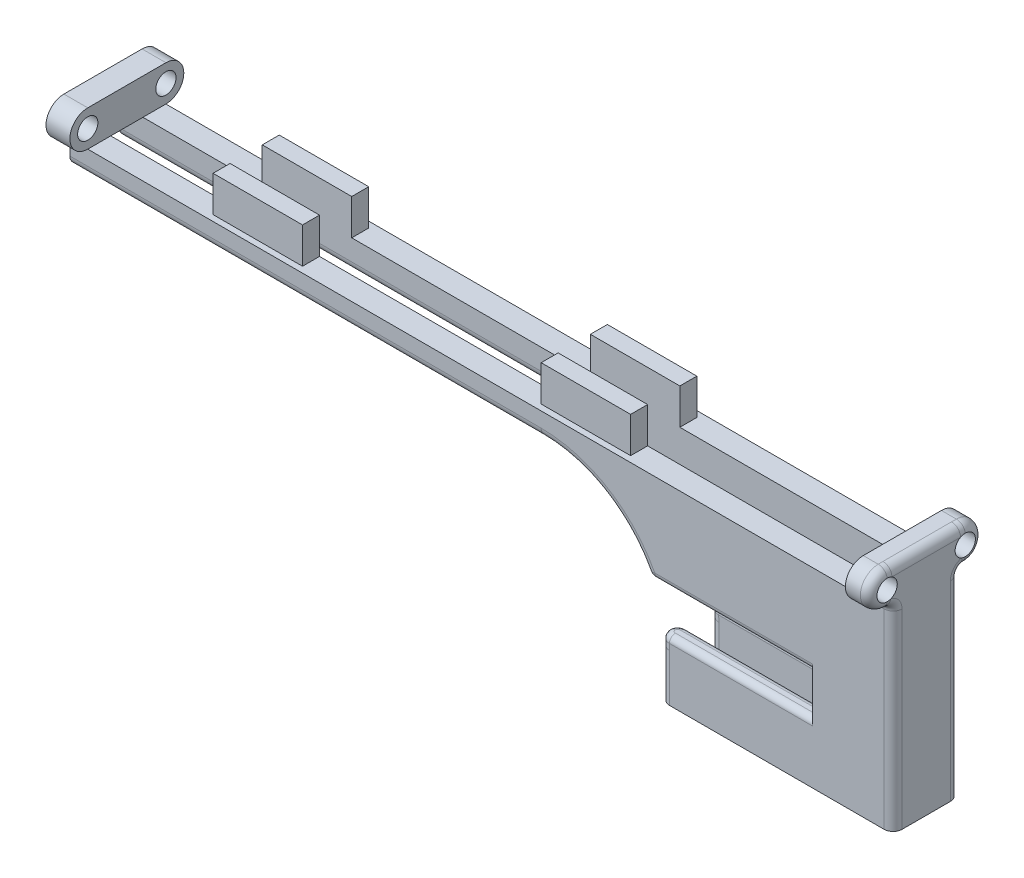
SolidWorks part; units mm, degrees
ref_plane "Plan de face" through (0, 0, 0) normal (0, 0, 1) x (1, 0, 0)
ref_plane "Plan de dessus" through (0, 0, 0) normal (0, 1, 0) x (1, 0, 0)
ref_plane "Plan de droite" through (0, 0, 0) normal (1, 0, 0) x (0, 0, -1)
sketch "Esquisse1" plane through (0, 0, 0) normal (0, 0, 1) x (1, 0, 0)
  line L0 (70, -6) -> (-40, -6) construction
  line L1 (25, -11) -> (-50, -11)
  line L3 (69.5003, -6) -> (40, -6)
  line L4 (-50, -11) -> (-50, -6)
  line L5 (69.5003, -6) -> (80, -6)
  line L6 (80, -6) -> (80, -31.0352)
  line L7 (70, -6) -> (-40, -6) construction
  line L8 (-50, 0) -> (-50, -6) construction
  line L9 (-30, -6) -> (-50, -6)
  line L11 (40, -6) -> (40, 0)
  line L12 (40, 0) -> (25, 0)
  line L13 (25, -6) -> (25, 0)
  line L15 (-15, -6) -> (-15, 0)
  line L16 (-15, 0) -> (-30, 0)
  line L17 (-30, -6) -> (-30, 0)
  line L18 (25, -6) -> (-15, -6)
  line L19 (40, 0) -> (40, -6) construction
  line L20 (40, 0) -> (40, -6) construction
  line L21 (-15, 0) -> (-15, -6) construction
  line L22 (45.0352, -31.0352) -> (80, -31.0352) construction
  line L23 (70.5, -22) -> (42.8822, -22)
  line L25 (70.5, -29) -> (70.5, -22)
  line L26 (70.5, -29) -> (44.9316, -29)
  line L28 (42.0815, -22.5) -> (16.9546, -22.5) construction
  line L32 (42.0815, -28.5) -> (16.9546, -28.5) construction
  line L33 (80, -31.0352) -> (80, -39)
  line L34 (80, -39) -> (45.0352, -39)
  line L35 (45.0352, -39) -> (45.0352, -31.0352)
  arc A4 (45.0352, -31.0352) -> (44.9316, -29) centre (25, -31.0352) ccw
  arc A5 (42.8822, -22) -> (25, -11) centre (25, -31.0352) ccw
  point P0 (24.6877, -7.875)
  dimension "D9" = 20.0352
  dimension "D1" = 5
  dimension "D6" = 75
  dimension "D7" = 0.5
  dimension "D8" = 0.5
  dimension "D10" = 9.5
  dimension "D11" = 10
extrude "Boss.-Extru.1" add sketch "Esquisse1" along normal blind 2.85
sketch "Esquisse2" plane through (80, 0, 0) normal (1, 0, 0) x (0, 0, -1)
  line L0 (0, -6) -> (1, -6)
  line L1 (0, -6) -> (0, -7)
  line L2 (0, -39) -> (0, -6) construction
  arc A0 (1, -6) -> (0, -7) centre (1, -7) ccw
  dimension "D1" = 1
extrude "Boss.-Extru.2" add sketch "Esquisse2" against normal up to surface (130 mm away) up to face at (-50, -8.5, 1.425)
ref_plane "Plan1" through (0, 0, 5.55) normal (0, 0, 1) x (1, 0, 0)
mirror "Symétrie4" about plane through (0, 0, 5.55) normal (0, 0, 1) of bodies 102
sketch "Esquisse3" plane through (80, 0, 0) normal (1, 0, 0) x (0, 0, -1)
  line L0 (0, -39) -> (0, -7) construction
  line L2 (-11.1, -39) -> (-11.1, -7) construction
  line L4 (0, -39) -> (0, -7)
  line L6 (-11.1, -39) -> (-11.1, -7)
  line L10 (-12.1, -6) -> (-12.1, 0) construction
  line L13 (78.6, 0) -> (-89.5, 0) construction
  line L14 (-5.55, 17.0694) -> (-5.55, -17.0694) construction
  line L15 (-12.1, 0) -> (1, 0)
  line L17 (0, -39) -> (-11.1, -39)
  arc A0 (1, -6) -> (0, -7) centre (1, -7) ccw construction
  arc A1 (-11.1, -7) -> (-12.1, -6) centre (-12.1, -7) ccw construction
  arc A2 (1, -6) -> (0, -7) centre (1, -7) ccw
  arc A3 (-11.1, -7) -> (-12.1, -6) centre (-12.1, -7) ccw
  arc A4 (-12.1, 0) -> (-12.1, -6) centre (-12.1, -3) ccw
  arc A5 (1, 0) -> (1, -6) centre (1, -3) cw
extrude "Boss.-Extru.3" add sketch "Esquisse3" along normal blind 4
hole_wizard "Dégagement M31" positions "Esquisse4" profile "Esquisse5" hole size "M3" standard "ISO" end condition up to next
sketch "Esquisse4" plane through (84, 0, 0) normal (1, 0, 0) x (0, 0, -1)
  point P0 (1, -3)
  point P3 (-12.1, -3)
sketch "Esquisse5" plane through (84, -3, -1) normal (0, 1, 0) x (0, 0, -1)
  line L0 (0, 0) -> (0, 4)
  line L1 (0, 4) -> (1.7, 4)
  line L2 (1.7, 4) -> (1.7, 0)
  line L5 (1.7, 0) -> (0, 0)
  line L11 (0, -6.35) -> (0, 107.95) construction
  dimension "Diamètre du perçage jusqu'au prochain" = 3.4
  dimension "Profondeur du perçage jusqu'au prochain" = 4
fillet "Congé1" radius 1.5 21 edges at (84, -23, 11.1) (84, -6.2929, 11.3929) (84, 0, 5.55) (84, -6.2929, -0.2929) (84, -23, 0) (45.0093, -30.0163, 0) (45.0093, -30.0163, 2.85) (45.0093, -30.0163, 11.1) (45.0093, -30.0163, 8.25) (-12.5, -11, 11.1) (35.4973, -13.9702, 11.1) (35.4973, -13.9702, 0) (-12.5, -11, 0) (-12.5, -11, 2.85) (35.4973, -13.9702, 2.85) (35.4973, -13.9702, 8.25) (-12.5, -11, 8.25) (45.0352, -35.0176, 0) (45.0352, -35.0176, 2.85) (45.0352, -35.0176, 11.1) (45.0352, -35.0176, 8.25)
fillet "Congé2" radius 1 16 edges at (43.188, -22, 0.6366) (43.4219, -22, 2.4527) (43.188, -22, 8.8866) (43.4219, -22, 10.7027) (58.4694, -29, 8.25) (57.5241, -22, 0) (57.5241, -22, 2.85) (57.5241, -22, 8.25) (57.5241, -22, 11.1) (58.4694, -29, 2.85) (58.4694, -29, 0) (58.4694, -29, 11.1) (45.2591, -29, 10.5335) (45.494, -29, 8.5814) (45.2591, -29, 2.2835) (45.494, -29, 0.3314)
sketch "Esquisse6" plane through (-50, 0, 0) normal (-1, 0, 0) x (0, 0, 1)
  line L0 (-1, 0) -> (12.1, 0) construction
  line L1 (11.1, -7) -> (11.1, -9.5) construction
  line L2 (8.25, -6) -> (8.25, -9.5) construction
  line L3 (2.85, -6) -> (2.85, -9.5) construction
  line L4 (0, -7) -> (0, -9.5) construction
  line L5 (-1, 0) -> (12.1, 0)
  line L6 (11.1, -7) -> (11.1, -9.5)
  line L7 (8.25, -6) -> (8.25, -9.5)
  line L8 (2.85, -6) -> (2.85, -9.5)
  line L9 (0, -7) -> (0, -9.5)
  line L10 (2.85, -6) -> (8.25, -6)
  circle A0 centre (12.1, -3) radius 1.7 construction
  circle A1 centre (-1, -3) radius 1.7 construction
  arc A2 (-1, 0) -> (-1, -6) centre (-1, -3) ccw construction
  arc A3 (12.1, -6) -> (12.1, 0) centre (12.1, -3) ccw construction
  arc A4 (12.1, -6) -> (11.1, -7) centre (12.1, -7) ccw construction
  arc A5 (9.675, -10.9981) -> (11.1, -9.5) centre (9.6, -9.5) ccw construction
  arc A6 (8.25, -9.5) -> (9.675, -10.9981) centre (9.75, -9.5) ccw construction
  arc A7 (1.425, -10.9981) -> (2.85, -9.5) centre (1.35, -9.5) ccw construction
  arc A8 (0, -7) -> (-1, -6) centre (-1, -7) ccw construction
  arc A9 (0, -9.5) -> (1.425, -10.9981) centre (1.5, -9.5) ccw construction
  circle A10 centre (12.1, -3) radius 1.7
  circle A11 centre (-1, -3) radius 1.7
  arc A12 (-1, 0) -> (-1, -6) centre (-1, -3) ccw
  arc A13 (12.1, -6) -> (12.1, 0) centre (12.1, -3) ccw
  arc A14 (12.1, -6) -> (11.1, -7) centre (12.1, -7) ccw
  arc A15 (9.675, -10.9981) -> (11.1, -9.5) centre (9.6, -9.5) ccw
  arc A16 (8.25, -9.5) -> (9.675, -10.9981) centre (9.75, -9.5) ccw
  arc A17 (1.425, -10.9981) -> (2.85, -9.5) centre (1.35, -9.5) ccw
  arc A18 (0, -7) -> (-1, -6) centre (-1, -7) ccw
  arc A19 (0, -9.5) -> (1.425, -10.9981) centre (1.5, -9.5) ccw
extrude "Boss.-Extru.4" add sketch "Esquisse6" along normal blind 4
